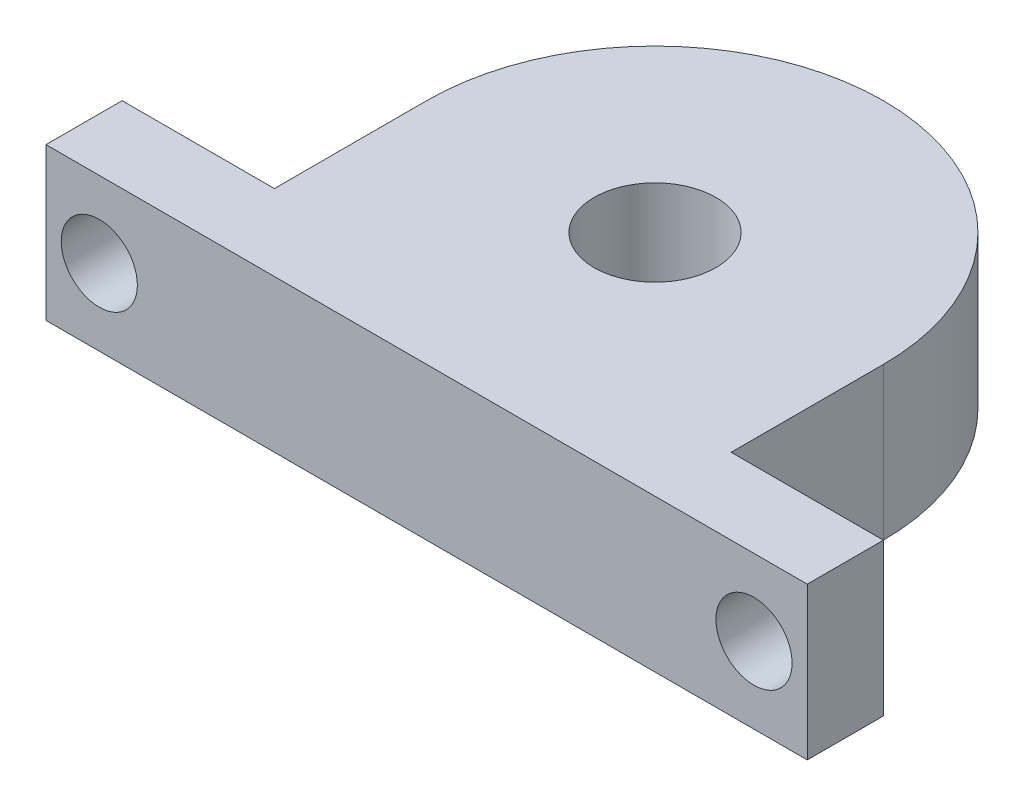
SolidWorks part; units mm, degrees
ref_plane "Plano frontal" through (0, 0, 0) normal (0, 0, 1) x (1, 0, 0)
ref_plane "Plano superior" through (0, 0, 0) normal (0, 1, 0) x (1, 0, 0)
ref_plane "Plano direito" through (0, 0, 0) normal (1, 0, 0) x (0, 0, -1)
sketch "Esboço1" plane through (0, 0, 0) normal (0, 1, 0) x (1, 0, 0)
  line L0 (-15, 0) -> (-15, -10)
  line L1 (-25, -15) -> (25, -15)
  line L2 (-25, -15) -> (-25, -10)
  line L4 (25, -15) -> (25, -10)
  line L5 (15, 0) -> (15, -10)
  line L6 (-15, -10) -> (-25, -10)
  line L7 (25, -10) -> (15, -10)
  arc A0 (-15, 0) -> (15, 0) centre (0, 0) cw
  point P3 (0, 0)
  point P9 (0, 0)
extrude "Ressalto-extrusão1" add sketch "Esboço1" along normal blind 5 and the other way blind 5
sketch "Esboço2" plane through (0, 0, 0) normal (0, 1, 0) x (1, 0, 0)
  circle A0 centre (0, 0) radius 4
extrude "Corte-extrusão1" cut sketch "Esboço2" against normal blind 5 and the other way blind 5
sketch "Esboço3" plane through (0, 0, 0) normal (0, 0, 1) x (1, 0, 0)
  circle A0 centre (21.5, 0) radius 2.5
  circle A1 centre (-21.5, 0) radius 2.5
extrude "Corte-extrusão2" cut sketch "Esboço3" along normal through all
